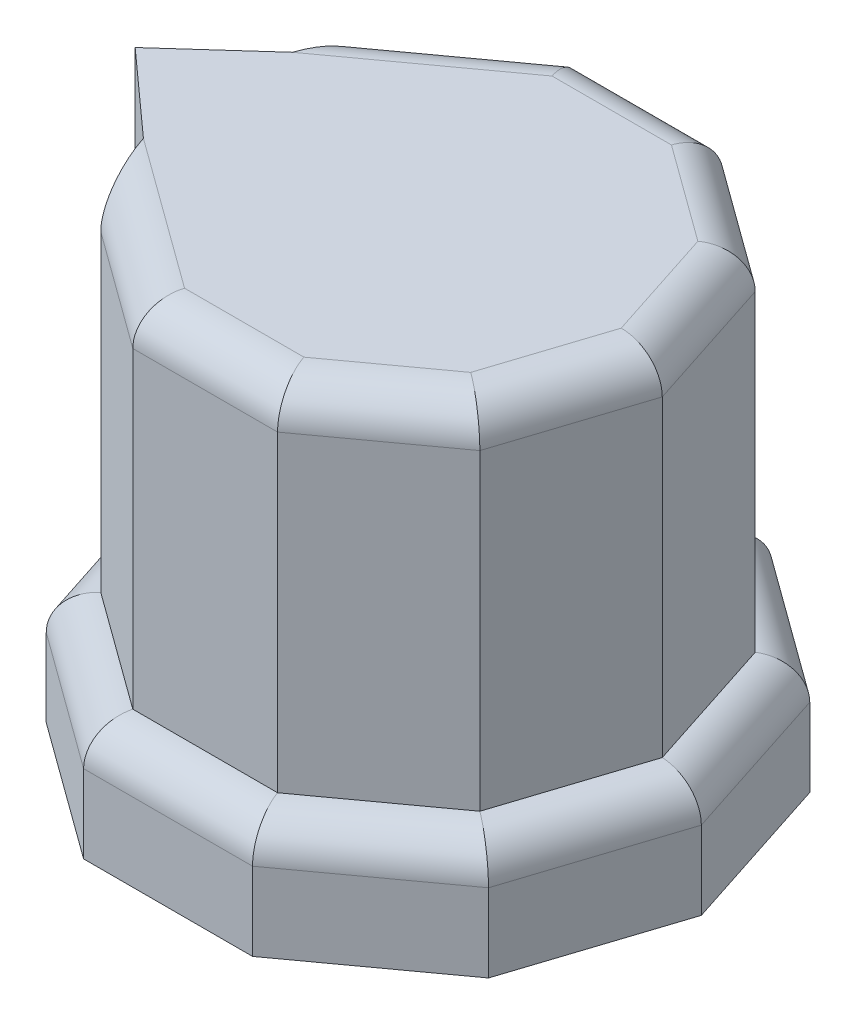
SolidWorks part; units mm, degrees
ref_plane "Front Plane" through (0, 0, 0) normal (0, 0, 1) x (1, 0, 0)
ref_plane "Top Plane" through (0, 0, 0) normal (0, 1, 0) x (1, 0, 0)
ref_plane "Right Plane" through (0, 0, 0) normal (1, 0, 0) x (0, 0, -1)
sketch "Sketch1" plane through (0, 0, 0) normal (0, 1, 0) x (1, 0, 0)
  line L0 (-5.6631, -4.1145) -> (-2.1631, -6.6574)
  line L1 (7, 0) -> (5.6631, 4.1145)
  line L2 (5.6631, 4.1145) -> (2.1631, 6.6574)
  line L3 (2.1631, 6.6574) -> (-2.1631, 6.6574)
  line L4 (-2.1631, 6.6574) -> (-5.6631, 4.1145)
  line L5 (-5.6631, 4.1145) -> (-7, 0)
  line L6 (-7, 0) -> (-5.6631, -4.1145)
  line L7 (-2.1631, -6.6574) -> (2.1631, -6.6574)
  line L8 (2.1631, -6.6574) -> (5.6631, -4.1145)
  line L9 (5.6631, -4.1145) -> (7, 0)
  circle A0 centre (0, 0) radius 6.6574 construction
  dimension "D1" = 7
extrude "Boss-Extrude1" add sketch "Sketch1" along normal blind 3
sketch "Sketch2" plane through (0, 3, 0) normal (0, 1, 0) x (1, 0, 0)
  line L1 (6, 0) -> (4.8541, 3.5267)
  line L2 (4.8541, 3.5267) -> (1.8541, 5.7063)
  line L3 (1.8541, 5.7063) -> (-1.8541, 5.7063)
  line L4 (-1.8541, 5.7063) -> (-4.8541, 3.5267)
  line L5 (-4.8541, 3.5267) -> (-6, 0)
  line L6 (-6, 0) -> (-4.8541, -3.5267)
  line L7 (-4.8541, -3.5267) -> (-1.8541, -5.7063)
  line L8 (-1.8541, -5.7063) -> (1.8541, -5.7063)
  line L9 (1.8541, -5.7063) -> (4.8541, -3.5267)
  line L10 (4.8541, -3.5267) -> (6, 0)
  circle A0 centre (0, 0) radius 5.7063 construction
  dimension "D1" = 6
extrude "Boss-Extrude2" add sketch "Sketch2" along normal blind 9
fillet "Fillet1" radius 1 10 edges at (-6.3316, 3, -2.0572) (-3.9131, 3, -5.3859) (-6.3316, 3, 2.0572) (0, 3, -6.6574) (3.9131, 3, -5.3859) (6.3316, 3, -2.0572) (6.3316, 3, 2.0572) (3.9131, 3, 5.3859) (0, 3, 6.6574) (-3.9131, 3, 5.3859)
sketch "Sketch3" plane through (0, 0, 0) normal (0, -1, 0) x (-1, 0, 0)
  line L0 (-3.45, 0) -> (1.55, 0)
  line L1 (1.55, -3.0822) -> (1.55, 3.0822)
  circle A0 centre (0, 0) radius 3.45
  point P8 (1.55, 0)
  dimension "D1" = 6.9
  dimension "D2" = 5
extrude "Cut-Extrude1" cut sketch "Sketch3" against normal blind 7 contours L0 A0 L1 | L1 A0 L0 region at (0.6727, 0, -1.5363) region at (0.6727, 0, 1.5363)
fillet "Fillet2" radius 1 8 edges at (-3.3541, 12, -4.6165) (0, 12, -5.7063) (3.3541, 12, -4.6165) (5.4271, 12, -1.7634) (5.4271, 12, 1.7634) (3.3541, 12, 4.6165) (0, 12, 5.7063) (-3.3541, 12, 4.6165)
sketch "Sketch4" plane through (0, 12, 0) normal (0, 1, 0) x (1, 0, 0)
  line L0 (-5.3798, -1.9087) -> (-7.5, 0)
  line L1 (-7.5, 0) -> (-5.3798, 1.9087)
  line L2 (-5.3798, -1.9087) -> (-5.3798, 1.9087)
  dimension "D1" = 1.5
extrude "Boss-Extrude3" add sketch "Sketch4" against normal blind 12
